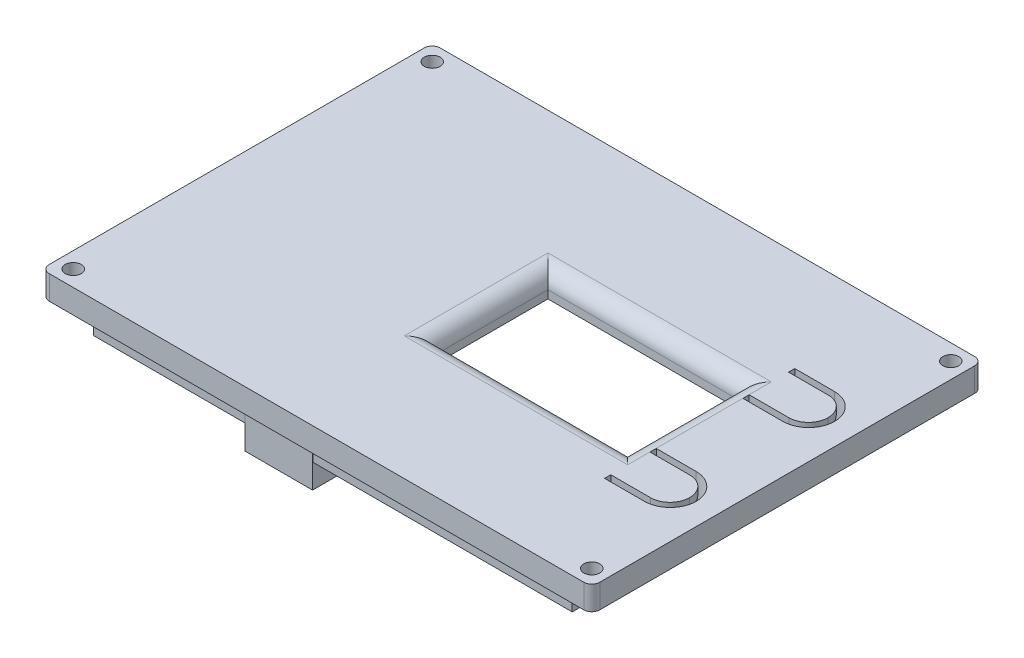
SolidWorks part; units mm, degrees
ref_plane "Piano frontale" through (0, 0, 0) normal (0, 0, 1) x (1, 0, 0)
ref_plane "Piano superiore" through (0, 0, 0) normal (0, 1, 0) x (1, 0, 0)
ref_plane "Piano destro" through (0, 0, 0) normal (1, 0, 0) x (0, 0, -1)
sketch "Schizzo1" plane through (0, 0, 0) normal (0, 1, 0) x (1, 0, 0)
  line L0 (0, 42.4246) -> (0, -46.0276) construction
  line L1 (-55.0349, 0) -> (84.3088, 0) construction
  line L3 (-34.5, 24.5) -> (34.5, 24.5)
  line L4 (-34.5, 24.5) -> (-34.5, -24.5)
  line L5 (-34.5, -24.5) -> (34.5, -24.5)
  line L6 (34.5, 24.5) -> (34.5, -24.5)
  line L7 (-34.5, 24.5) -> (34.5, -24.5) construction
  line L8 (-34.5, -24.5) -> (34.5, 24.5) construction
  point P5 (0, 0)
  dimension "D1" = 49
  dimension "D2" = 69
extrude "Estrusione-Estrusione1" add sketch "Schizzo1" along normal blind 3
fillet "Raccordo1" radius 1 1 edges at (-34.5, 1.5, 24.5) type face fillet first side face at (0, 1.5, 24.5) second side face at (-34.5, 1.5, 0)
fillet "Raccordo2" radius 1 1 edges at (-34.5, 1.5, -24.5) type face fillet first side face at (0, 1.5, -24.5) second side face at (-34.5, 1.5, -0.5)
fillet "Raccordo3" radius 1 1 edges at (34.5, 1.5, 24.5) type face fillet first side face at (0.5, 1.5, 24.5) second side face at (34.5, 1.5, 0)
fillet "Raccordo4" radius 1 1 edges at (34.5, 1.5, -24.5) type face fillet first side face at (34.5, 1.5, -0.5) second side face at (0.5, 1.5, -24.5)
sketch "Schizzo2" plane through (0, 0, 0) normal (0, -1, 0) x (1, 0, 0)
  line L0 (-42.5418, 0) -> (48.8884, 0) construction
  line L1 (0, 27.8158) -> (0, -29.0554) construction
  line L2 (-33.5, 24.5) -> (33.5, 24.5) construction
  line L3 (-30, 22.45) -> (30, 22.45)
  line L4 (-30, 22.45) -> (-30, 20.2188)
  line L5 (-30, 20.2188) -> (30, 20.2188)
  line L6 (30, 22.45) -> (30, 20.2188)
  line L7 (-34.5, -23.5) -> (-34.5, 23.5) construction
  line L9 (30, -22.45) -> (30, -20.2188)
  line L10 (-30, -20.2188) -> (30, -20.2188)
  line L11 (-30, -22.45) -> (-30, -20.2188)
  line L12 (-30, -22.45) -> (30, -22.45)
  dimension "D1" = 2.05
  dimension "D2" = 60
  dimension "D3" = 4.5
extrude "Estrusione-Estrusione2" add sketch "Schizzo2" along normal blind 3
fillet "Raccordo5" radius 3 1 edges at (0, 0, 20.2188) type face fillet first side face at (0, -1.5, 20.2188) second side face at (0, 0, 21.3344)
fillet "Raccordo6" radius 3 1 edges at (0, 0, -20.2188) type face fillet first side face at (0, -1.5, -20.2188) second side face at (0, 0, 19.8344)
sketch "Schizzo3" plane through (0, 3, 0) normal (0, 1, 0) x (1, 0, 0)
  line L0 (-41.7981, 0) -> (51.2684, 0) construction
  line L1 (33.5, 24.5) -> (-33.5, 24.5) construction
  line L2 (-41.7981, 22.5) -> (47.3513, 22.5) construction
  line L3 (-32.5, 28.6091) -> (-32.5, -28.1629) construction
  line L4 (-34.5, 23.5) -> (-34.5, -23.5) construction
  line L5 (0, 34.5533) -> (0, -28.7605) construction
  circle A0 centre (-32.5, 22.5) radius 1
  circle A1 centre (32.5, 22.5) radius 1
  circle A2 centre (32.5, -22.5) radius 1
  circle A3 centre (-32.5, -22.5) radius 1
  dimension "D3" = 2
  dimension "D1" = 2
  dimension "D2" = 2
extrude "Taglio-Estrusione1" cut sketch "Schizzo3" against normal up to surface (3 mm away) up to face at (0, 0, 19.8344)
sketch "Schizzo4" plane through (0, 0, 0) normal (0, -1, 0) x (1, 0, 0)
  line L0 (-38.2777, 0) -> (44.5251, 0) construction
  line L1 (0, 26.5762) -> (0, -28.4108) construction
  line L7 (34.5, 23.5) -> (34.5, -23.5) construction
  line L10 (21.5, 7) -> (-2.5, 7)
  line L11 (21.5, 7) -> (21.5, -7)
  line L12 (21.5, -7) -> (-2.5, -7)
  line L13 (-2.5, 7) -> (-2.5, -7)
  point P6 (0, 0)
  dimension "D1" = 24
  dimension "D2" = 14
  dimension "D3" = 13
extrude "Taglio-Estrusione2" cut sketch "Schizzo4" against normal up to surface (3 mm away) up to face at (-32.5, 3, 21.5)
sketch "Schizzo5" plane through (0, 0, 0) normal (0, -1, 0) x (1, 0, 0)
  line L0 (-39.7156, 0) -> (46.9547, 0) construction
  line L1 (34.5, 23.5) -> (34.5, -23.5) construction
  line L2 (-33, 11.5) -> (-10, 11.5)
  line L3 (-33, 11.5) -> (-33, -11.5)
  line L4 (-33, -11.5) -> (-10, -11.5)
  line L5 (-10, 11.5) -> (-10, -11.5)
  line L6 (-33, 11.5) -> (-10, -11.5) construction
  line L7 (-33, -11.5) -> (-10, 11.5) construction
  point P3 (-21.5, 0)
  dimension "D1" = 23
  dimension "D2" = 23
  dimension "D3" = 44.5
extrude "Taglio-Estrusione3" cut sketch "Schizzo5" against normal blind 1.2
fillet "Raccordo7" radius 0.5 1 edges at (-33, 0.6, 11.5) type face fillet first side face at (-33, 0.6, 0) second side face at (-21.5, 0.6, 11.5)
fillet "Raccordo8" radius 0.5 1 edges at (-10, 0.6, 11.5) type face fillet first side face at (-21.25, 0.6, 11.5) second side face at (-10, 0.6, 0)
fillet "Raccordo9" radius 0.5 1 edges at (-33, 0.6, -11.5) type face fillet first side face at (-33, 0.6, -0.25) second side face at (-21.5, 0.6, -11.5)
fillet "Raccordo10" radius 0.5 1 edges at (-10, 0.6, -11.5) type face fillet first side face at (-10, 0.6, -0.25) second side face at (-21.25, 0.6, -11.5)
fillet "Raccordo11" radius 2 1 edges at (21.5, 3, 0) type face fillet first side face at (9.5, 3, 0) second side face at (21.5, 1.5, 0)
fillet "Raccordo12" radius 2 1 edges at (10.5, 3, 7) type face fillet first side face at (12.2172, 1.4828, 7) second side face at (10.5, 3, 0)
fillet "Raccordo13" radius 2 1 edges at (-2.5, 3, 1) type face fillet first side face at (10.5, 3, 1) second side face at (-2.5, 1.4828, 1.7172)
fillet "Raccordo14" radius 2 1 edges at (9.5, 3, -7) type face fillet first side face at (9.5, 3, 1) second side face at (9.5, 1.4714, -7)
sketch "Schizzo6" plane through (0, 0, 0) normal (0, -1, 0) x (1, 0, 0)
  line L0 (-2.5, 26.5762) -> (-2.5, -28.3116) construction
  line L1 (-43.7318, 0) -> (48.8388, 0) construction
  line L2 (-34.5, -23.5) -> (-34.5, 23.5) construction
  line L13 (-33.5, 24.5) -> (33.5, 24.5) construction
  line L14 (-2.5, 22.5) -> (-10.9441, 22.5)
  line L15 (-2.5, 22.5) -> (-2.5, 14.25)
  line L16 (-2.5, 14.25) -> (-10.9441, 14.25)
  line L17 (-10.9441, 22.5) -> (-10.9441, 14.25)
  line L18 (-10.9441, -22.5) -> (-10.9441, -14.25)
  line L19 (-2.5, -14.25) -> (-10.9441, -14.25)
  line L20 (-2.5, -22.5) -> (-2.5, -14.25)
  line L21 (-2.5, -22.5) -> (-10.9441, -22.5)
  dimension "D1" = 32
  dimension "D2" = 8.25
  dimension "D3" = 2
extrude "Estrusione-Estrusione3" add sketch "Schizzo6" along normal blind 6
sketch "Schizzo7" plane through (0, -6, 0) normal (0, -1, 0) x (1, 0, 0)
  line L0 (-41.2031, 0) -> (55.4829, 0) construction
  line L1 (-6.72, 24.8689) -> (-6.72, 12.8204) construction
  line L2 (-10.0246, 18.375) -> (-1.9426, 18.375) construction
  line L5 (-2.5, 14.25) -> (-2.5, 22.5) construction
  line L7 (-2.5, 22.5) -> (-10.9441, 22.5) construction
  circle A0 centre (-6.72, 18.375) radius 0.9
  circle A2 centre (-6.72, -18.375) radius 0.9
  dimension "D1" = 4.22
  dimension "D3" = 1.8
  dimension "D2" = 4.125
extrude "Taglio-Estrusione4" cut sketch "Schizzo7" against normal up to surface (6 mm away) up to face at (-21.5, 0, 0)
sketch "Schizzo8" plane through (0, 0, 0) normal (0, -1, 0) x (1, 0, 0)
  line L0 (-45.6655, 0) -> (51.1196, 0) construction
  line L1 (-45.6655, 14) -> (51.9625, 14) construction
  line L2 (-33.5, 24.5) -> (33.5, 24.5) construction
  line L3 (-49.9792, 8.7) -> (50.2271, 8.7) construction
  line L4 (28.5, 28.51) -> (28.5, -29.452) construction
  line L5 (21.5, -7) -> (21.5, 7) construction
  circle A0 centre (28.5, 8.7) radius 1.75
  circle A1 centre (28.5, -8.7) radius 1.75
  dimension "D5" = 3.5
  dimension "D1" = 24.5
  dimension "D2" = 14
  dimension "D3" = 5.3
  dimension "D4" = 7
extrude "Estrusione-Estrusione4" add sketch "Schizzo8" along normal blind 1.2 and the other way up to surface (3 mm away) other way up to face at (9.5, 3, 0)
sketch "Schizzo9" plane through (0, 0, 0) normal (0, -1, 0) x (1, 0, 0)
  line L0 (32.2287, 8.6769) -> (9.4207, 8.6769) construction
  line L1 (38.0794, 0) -> (-43.4839, 0) construction
  line L2 (28.5231, 11.1395) -> (23.5222, 11.1395)
  line L3 (28.5231, 6.2144) -> (23.5222, 6.2144)
  line L4 (28.4769, 11.9206) -> (23.5222, 11.9206)
  line L5 (23.5222, 11.9206) -> (23.5222, 11.1395)
  line L6 (28.4769, 5.4333) -> (23.5222, 5.4333)
  line L7 (23.5222, 5.4333) -> (23.5222, 6.2144)
  line L8 (23.5222, -5.4333) -> (23.5222, -6.2144)
  line L9 (28.4769, -5.4333) -> (23.5222, -5.4333)
  line L10 (23.5222, -11.9206) -> (23.5222, -11.1395)
  line L11 (28.4769, -11.9206) -> (23.5222, -11.9206)
  line L12 (28.5231, -6.2144) -> (23.5222, -6.2144)
  line L13 (28.5231, -11.1395) -> (23.5222, -11.1395)
  arc A0 (30.9395, 8.6769) -> (28.5231, 11.1395) centre (28.5, 8.7) ccw
  arc A1 (30.9395, 8.6769) -> (28.5231, 6.2144) centre (28.5, 8.6539) cw
  arc A2 (31.7667, 8.6769) -> (28.4769, 11.9206) centre (28.5, 8.6539) ccw
  arc A3 (31.7667, 8.6769) -> (28.4769, 5.4333) centre (28.5, 8.7) cw
  arc A4 (31.7667, -8.6769) -> (28.4769, -5.4333) centre (28.5, -8.7) ccw
  arc A5 (31.7667, -8.6769) -> (28.4769, -11.9206) centre (28.5, -8.6539) cw
  arc A6 (30.9395, -8.6769) -> (28.5231, -6.2144) centre (28.5, -8.6539) ccw
  arc A7 (30.9395, -8.6769) -> (28.5231, -11.1395) centre (28.5, -8.7) cw
extrude "Taglio-Estrusione5" cut sketch "Schizzo9" against normal up to surface (3 mm away) up to face at (9.5, 3, 0)
sketch "Schizzo11" plane through (0, 0, 0) normal (0, -1, 0) x (1, 0, 0)
  line L0 (23.5222, 14.4161) -> (23.5222, 1.6625) construction
  line L1 (28.5231, 11.1395) -> (23.5222, 11.1395)
  line L2 (23.5222, 11.1395) -> (28.5231, 11.1395) construction
  line L3 (23.5222, 11.1395) -> (23.5222, 6.2144)
  line L4 (23.5222, 6.2144) -> (28.5231, 6.2144)
  line L5 (22.1495, 8.7226) -> (38.5554, 8.7226) construction
  line L6 (41.7422, 0) -> (4.3017, 0) construction
  line L7 (23.5222, -6.2144) -> (28.5231, -6.2144)
  line L8 (23.5222, -11.1395) -> (23.5222, -6.2144)
  line L9 (28.5231, -11.1395) -> (23.5222, -11.1395)
  arc A0 (28.5231, 11.1395) -> (30.9395, 8.6769) centre (28.5231, 8.7226) cw
  arc A1 (28.5231, 6.2144) -> (30.9395, 8.6769) centre (28.5231, 8.6313) ccw
  arc A2 (28.5231, -6.2144) -> (30.9395, -8.6769) centre (28.5231, -8.6313) cw
  arc A3 (28.5231, -11.1395) -> (30.9395, -8.6769) centre (28.5231, -8.7226) ccw
extrude "Taglio-Estrusione6" cut sketch "Schizzo11" against normal blind 2
sketch "Schizzo13" plane through (0, 2, 0) normal (0, -1, 0) x (1, 0, 0)
  circle A0 centre (28.5, 8.7) radius 1.9
extrude "Estrusione-Estrusione5" add sketch "Schizzo13" along normal up to surface (3.2 mm away) up to face at (28.5, -1.2, 6.95)
sketch "Schizzo14" plane through (0, 2, 0) normal (0, -1, 0) x (1, 0, 0)
  circle A0 centre (28.5, -8.7) radius 1.9
extrude "Estrusione-Estrusione6" add sketch "Schizzo14" along normal up to surface (3.2 mm away) up to face at (28.5, -1.2, -6.95)
equation "\".5.00mm\"=3"
